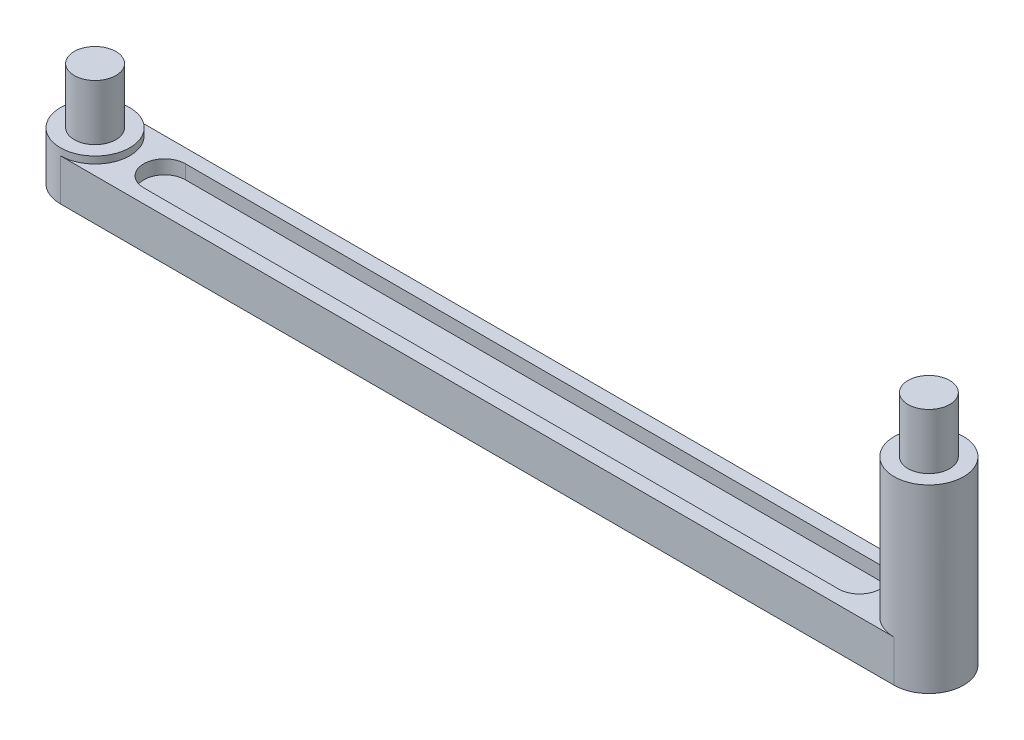
SolidWorks part; units mm, degrees
material "ABS"
ref_plane "Спереди" through (0, 0, 0) normal (0, 0, 1) x (1, 0, 0)
ref_plane "Сверху" through (0, 0, 0) normal (0, 1, 0) x (1, 0, 0)
ref_plane "Справа" through (0, 0, 0) normal (1, 0, 0) x (0, 0, -1)
sketch "Эскиз1" plane through (0, 0, 0) normal (0, 1, 0) x (1, 0, 0)
  line L0 (30, 0) -> (-30, 0) construction
  line L1 (30, -2.5) -> (-30, -2.5)
  line L2 (30, 2.5) -> (-30, 2.5)
  arc A0 (30, -2.5) -> (30, 2.5) centre (30, 0) ccw
  arc A1 (-30, 2.5) -> (-30, -2.5) centre (-30, 0) ccw
  circle A2 centre (-30, 0) radius 2 construction
  point P2 (0, 0)
  dimension "D2" = 4
  dimension "D3" = 0.5
  dimension "D1" = 60
extrude "Бобышка-Вытянуть1" add sketch "Эскиз1" along normal blind 3
sketch "Эскиз2" plane through (0, 3, 0) normal (0, 1, 0) x (1, 0, 0)
  circle A0 centre (-30, 0) radius 2.5
  circle A1 centre (30, 0) radius 2.5
  arc M1 (30, -2.5) -> (30, 2.5) centre (30, 0) ccw
  arc M3 (-30, 2.5) -> (-30, -2.5) centre (-30, 0) ccw
extrude "Бобышка-Вытянуть2" add sketch "Эскиз2" along normal blind 0.5 contours A0 M3 region at (-30, 3, 0)
sketch "Эскиз3" plane through (0, 3, 0) normal (0, 1, 0) x (1, 0, 0)
  circle A0 centre (-30, 0) radius 1.5
  circle A1 centre (30, 0) radius 1.5
  dimension "D2" = 3
extrude "Бобышка-Вытянуть3" add sketch "Эскиз3" along normal offset from surface (4.5 mm away) 4 contours A0 region at (-30, 3, 0) up to face at (-30, 3.5, 2.5) offset beyond the face yes
extrude "Бобышка-Вытянуть4" add sketch "Эскиз2<3>" along normal blind 10 contours A1 M1 region at (30, 3, 0)
sketch "Эскиз2<3>" plane through (0, 3, 0) normal (0, 1, 0) x (1, 0, 0) same geometry as "Эскиз2"
extrude "Бобышка-Вытянуть5" add sketch "Эскиз3<3>" along normal offset from surface (14 mm away) 4 contours A1 region at (30, 3, 0) up to face at (30, 13, 2.5) offset beyond the face yes
sketch "Эскиз3<3>" plane through (0, 3, 0) normal (0, 1, 0) x (1, 0, 0) same geometry as "Эскиз3"
sketch "Эскиз4" plane through (0, 3, 0) normal (0, 1, 0) x (1, 0, 0)
  line L0 (25, 0) -> (-25, 0) construction
  line L1 (25, -1.5) -> (-25, -1.5)
  line L2 (25, 1.5) -> (-25, 1.5)
  line L3 (-25, 1.5) -> (-25, 2.5) construction
  line L4 (30, 2.5) -> (-30, 2.5) construction
  line L6 (-26.5, 0) -> (-27.5, 0) construction
  arc A0 (25, -1.5) -> (25, 1.5) centre (25, 0) ccw
  arc A1 (-25, 1.5) -> (-25, -1.5) centre (-25, 0) ccw
  arc A2 (-30, -2.5) -> (-30, 2.5) centre (-30, 0) ccw construction
  point P2 (0, 0)
  dimension "D1" = 1
extrude "Вырез-Вытянуть1" cut sketch "Эскиз4" against normal offset from surface (1 mm away) 2 up to face at (0, 0, 0)
